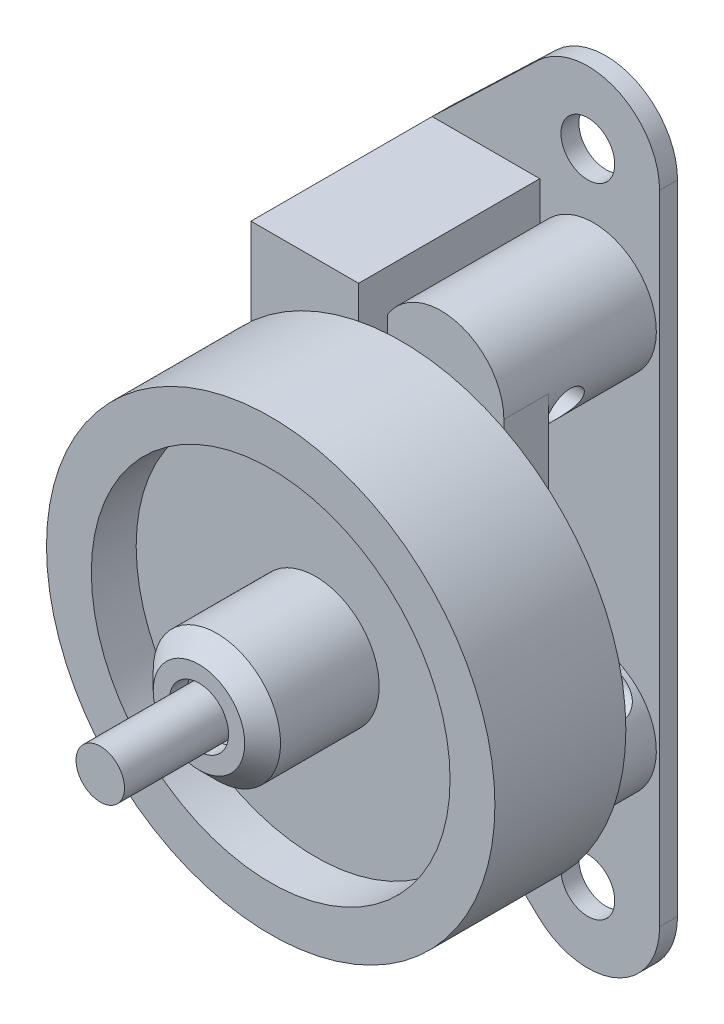
SolidWorks part; units mm, degrees
ref_plane "Front Plane" through (0, 0, 0) normal (0, 0, 1) x (1, 0, 0)
ref_plane "Top Plane" through (0, 0, 0) normal (0, 1, 0) x (1, 0, 0)
ref_plane "Right Plane" through (0, 0, 0) normal (1, 0, 0) x (0, 0, -1)
sketch "Sketch1" plane through (0, 0, 0) normal (0, 0, 1) x (1, 0, 0)
  line L0 (47.18, 17.78) -> (47.18, -17.78)
  line L1 (39.18, 17.78) -> (39.18, -17.78)
  circle A0 centre (43.18, 17.78) radius 1.5 construction
  circle A1 centre (43.18, 17.78) radius 1.5
  circle A2 centre (43.18, -17.78) radius 1.5 construction
  circle A3 centre (43.18, -17.78) radius 1.5
  circle A4 centre (43.18, 17.78) radius 4
  circle A5 centre (43.18, -17.78) radius 4
  dimension "D1" = 8
extrude "Boss-Extrude1" add sketch "Sketch1" along normal blind 1 contours A5 L0 A4 L1 | A4 A1 | A5 A3 region at (43.18, 13.8931, 0) region at (43.18, 0, 0) region at (43.18, -21.6669, 0)
sketch "Sketch2" plane through (0, 0, 1) normal (0, 0, 1) x (1, 0, 0)
  line L0 (40.4119, 20.6675) -> (34.5, 15)
  line L1 (34.5, 15) -> (34.5, -15)
  line L2 (34.5, -15) -> (40.4119, -20.6675)
  line L3 (39.18, 17.78) -> (39.18, -17.78) construction
  line L4 (39.18, 17.78) -> (39.18, -17.78)
  line L5 (48.5, -24.75) -> (48.5, 24.75) construction
  line L7 (34.5, 0) -> (39.18, 0) construction
  arc A0 (47.18, 17.78) -> (39.18, 17.78) centre (43.18, 17.78) ccw construction
  arc A1 (39.18, -17.78) -> (47.18, -17.78) centre (43.18, -17.78) ccw construction
  arc A2 (47.18, 17.78) -> (39.18, 17.78) centre (43.18, 17.78) ccw
  arc A3 (39.18, -17.78) -> (47.18, -17.78) centre (43.18, -17.78) ccw
  line M1 (39.18, 17.78) -> (39.18, -17.78)
  arc M2 (39.18, -17.78) -> (47.18, -17.78) centre (43.18, -17.78) ccw
  arc M4 (47.18, 17.78) -> (39.18, 17.78) centre (43.18, 17.78) ccw
  dimension "D1" = 14
  dimension "D2" = 30
extrude "Boss-Extrude2" add sketch "Sketch2" against normal blind 1 contours L1 L7 L0 M1 M4 | L7 L1 L2 L4 M2 region at (36.953, 8.7197, 1) region at (36.953, -8.7197, 1)
sketch "Sketch3" plane through (0, 0, 1) normal (0, 0, 1) x (1, 0, 0)
  line L0 (34.5, 15) -> (34.5, 11.5) construction
  line L1 (34.5, 15) -> (40.5, 15)
  line L2 (34.5, 15) -> (34.5, 6.75)
  line L3 (34.5, 6.75) -> (40.5, 6.75)
  line L4 (40.5, 15) -> (40.5, 6.75)
  line L5 (34.5, -15) -> (40.5, -15)
  line L6 (34.5, -15) -> (34.5, -3.75)
  line L7 (34.5, -3.75) -> (40.5, -3.75)
  line L8 (40.5, -15) -> (40.5, -3.75)
  line L9 (34.5, 11.5) -> (59.3702, 11.5) construction
  line L10 (34.5, -15) -> (34.5, -11.5) construction
  line L11 (34.5, -11.5) -> (58.5732, -11.5) construction
  line L12 (43.18, 17.78) -> (43.18, 11.5) construction
  line L13 (43.18, -17.78) -> (43.18, -11.5) construction
  dimension "D1" = 10.5
  dimension "D2" = 23
  dimension "D3" = 7.75
  dimension "D4" = 4.75
  dimension "D5" = 6
extrude "Boss-Extrude3" add sketch "Sketch3" along normal blind 7.1
sketch "Sketch4" plane through (0, 0, 1) normal (0, 0, 1) x (1, 0, 0)
  line L0 (37.5, 6.75) -> (37.5, -3.75) construction
  line L1 (34.5, 6.75) -> (40.5, 6.75) construction
  line L2 (40.5, -3.75) -> (34.5, -3.75) construction
  line L3 (37.5, 1.5) -> (43.5, 1.5) construction
  line L4 (34.5, 6.75) -> (34.5, -3.75) construction
  line L5 (40.5, 10.875) -> (56.47, 10.875) construction
  line L6 (40.5, 6.75) -> (40.5, 15) construction
  line L7 (40.5, -9.375) -> (56.47, -9.375) construction
  line L8 (40.5, -15) -> (40.5, -3.75) construction
  line L9 (43.5, 1.5) -> (43.5, -9.375) construction
  line L10 (43.5, 1.5) -> (43.5, 10.875) construction
  circle A0 centre (43.5, 1.5) radius 2.1
  circle A1 centre (43.5, 10.875) radius 3.5
  circle A2 centre (43.5, -9.375) radius 3.5
  line M3 (40.5, -3.75) -> (40.5, -15)
  line M11 (40.5, 15) -> (40.5, 6.75)
  dimension "D2" = 4.2
  dimension "D3" = 7
  dimension "D1" = 9
extrude "Boss-Extrude4" add sketch "Sketch4" along normal blind 6 contours A1 M11 | A2 M3 region at (43.6048, 10.875, 1) region at (43.6048, -9.375, 1)
sketch "Sketch5" plane through (0, 0, 7) normal (0, 0, 1) x (1, 0, 0)
  line L0 (47, 10.875) -> (47, -9.375)
  line L1 (40, 10.875) -> (40, -9.375)
  arc A0 (40.5, 9.0722) -> (40.5, 12.6778) centre (43.5, 10.875) ccw construction
  circle A1 centre (43.5, 10.875) radius 3.5
  arc A2 (40.5, -11.1778) -> (40.5, -7.5722) centre (43.5, -9.375) ccw construction
  circle A3 centre (43.5, -9.375) radius 3.5
  line M3 (40.5, 12.6778) -> (40.5, 9.0722)
  arc M4 (40.5, 9.0722) -> (40.5, 12.6778) centre (43.5, 10.875) ccw
extrude "Boss-Extrude5" add sketch "Sketch5" along normal blind 1.5 contours M4 M3 | A3 L0 A1 L1 M4 | A3 region at (43.6048, 10.875, 7) region at (43.5, 0.75, 7) region at (43.5, -9.375, 7)
extrude "Cut-Extrude1" cut sketch "Sketch4<3>" along normal blind 12 contours A0 region at (43.5, 1.5, 1)
sketch "Sketch4<3>" plane through (0, 0, 1) normal (0, 0, 1) x (1, 0, 0) same geometry as "Sketch4"
sketch "Sketch6" plane through (34.5, 0, 0) normal (-1, 0, 0) x (0, 0, 1)
  line L0 (8.1, 15) -> (8.1, 6.75) construction
  line L1 (8.1, 11.5) -> (0, 11.5) construction
  line L2 (8.1, 11.5) -> (8.1, -11.5) construction
  line L3 (8.1, -11.5) -> (0, -11.5) construction
  line L4 (0, 11.5) -> (0, -11.5) construction
  line L5 (0, 15) -> (0, -15) construction
  line L6 (8.1, -3.75) -> (8.1, -15) construction
  line L8 (0, 0) -> (8.1, 0) construction
  circle A0 centre (5.8, 9.5) radius 1
  circle A1 centre (2.3, -6.5) radius 1
  point P8 (0, 0)
  dimension "D2" = 16
  dimension "D3" = 2
  dimension "D1" = 23
  dimension "D4" = 2.3
  dimension "D5" = 2.3
  dimension "D6" = 2
  dimension "D7" = 5
extrude "Cut-Extrude2" cut sketch "Sketch6" against normal blind 13
sketch "Sketch7" plane through (0, 0, 8.5) normal (0, 0, 1) x (1, 0, 0)
  circle A0 centre (43.5, 1.5) radius 3.7
  dimension "D1" = 7.4
extrude "Boss-Extrude6" add sketch "Sketch7" along normal blind 3.2 separate body
sketch "Sketch8" plane through (0, 0, 11.7) normal (0, 0, 1) x (1, 0, 0)
  circle A0 centre (43.5, 1.5) radius 12.5
  dimension "D1" = 25
extrude "Boss-Extrude7" add sketch "Sketch8" along normal blind 7.3
sketch "Sketch9" plane through (0, 0, 19) normal (0, 0, 1) x (1, 0, 0)
  circle A0 centre (43.5, 1.5) radius 2
  dimension "D1" = 4
extrude "Boss-Extrude8" add sketch "Sketch9" along normal blind 1.8
sketch "Sketch10" plane through (0, 0, 20.8) normal (0, 0, 1) x (1, 0, 0)
  circle A0 centre (43.5, 1.5) radius 1.35
  dimension "D1" = 2.7
extrude "Boss-Extrude9" add sketch "Sketch10" along normal blind 7.7
sketch "Sketch11" plane through (0, 0, 8.1) normal (0, 0, 1) x (1, 0, 0)
  line L1 (40, 6.75) -> (40.5, 6.75)
  line L2 (40, 6.75) -> (40, 15)
  line L3 (40, 15) -> (40.5, 15)
  line L4 (34.5, 15) -> (34.5, 6.75)
  line L5 (34.5, 6.75) -> (40, 6.75)
  line L6 (40.5, 12.6778) -> (40.5, 15)
  line L7 (40.5, 15) -> (34.5, 15)
  line L8 (34.5, 15) -> (34.5, 6.75)
  line L9 (34.5, 6.75) -> (40, 6.75)
  line L10 (40.5, 12.6778) -> (40.5, 15)
  line L11 (40.5, 15) -> (34.5, 15)
  line L12 (34.5, -3.75) -> (34.5, -15)
  line L13 (34.5, -15) -> (40.5, -15)
  line L14 (40.5, -15) -> (40.5, -11.1778)
  line L15 (40, -3.75) -> (34.5, -3.75)
  line L16 (34.5, -3.75) -> (34.5, -15)
  line L17 (34.5, -15) -> (40.5, -15)
  line L18 (40.5, -15) -> (40.5, -11.1778)
  line L19 (40, -3.75) -> (34.5, -3.75)
  line L20 (40.5, 6.75) -> (40.5, 15)
  line L21 (40, -9.375) -> (40, -3.75)
  line L22 (40.5, 9.0722) -> (40.5, 12.6778)
  line L23 (40.5, 9.0722) -> (40.5, 12.6778)
  line L24 (40, 6.75) -> (40, 10.875)
  line L25 (40, 6.75) -> (40, 10.875)
  line L26 (40, -9.375) -> (40, -3.75)
  line L27 (40.5, -15) -> (40, -15)
  line L28 (40.5, -15) -> (40.5, -3.75)
  line L29 (40.5, -3.75) -> (40, -3.75)
  line L30 (40, -15) -> (40, -3.75)
  arc A1 (40, 10.875) -> (40.5, 9.0722) centre (43.5, 10.875) ccw
  arc A2 (40, 10.875) -> (40.5, 9.0722) centre (43.5, 10.875) ccw
  arc A3 (40, -9.375) -> (40.5, -11.1778) centre (43.5, -9.375) ccw
  arc A4 (40, -9.375) -> (40.5, -11.1778) centre (43.5, -9.375) ccw
  line M9 (34.5, 15) -> (34.5, 6.75)
  line M10 (34.5, 6.75) -> (40, 6.75)
  line M11 (40.5, 12.6778) -> (40.5, 15)
  line M12 (40.5, 15) -> (34.5, 15)
  arc M13 (40, 10.875) -> (40.5, 9.0722) centre (43.5, 10.875) ccw
  line M14 (40.5, 9.0722) -> (40.5, 12.6778)
  line M15 (40, 6.75) -> (40, 10.875)
  dimension "D1" = 0
  dimension "D2" = 0
extrude "Boss-Extrude10" add sketch "Sketch11" along normal blind 2 contours L17 L30 L26 L19 L16 | A4 L30 L17 L18 | L26 A4 L28 L29 | L2 M15 M12 M9 M10 | L1 L20 M13 M15 | L2 M13 M14 M11 M12 region at (40.2295, 8.2331, 8.1) region at (37.25, 10.875, 8.1) region at (40.2611, 12.3108, 8.1) region at (37.25, -9.375, 8.1) region at (40.2587, -7.1856, 8.1) region at (40.2365, -12.7774, 8.1)
sketch "Sketch13" plane through (0, 0, 1) normal (0, 0, 1) x (1, 0, 0)
  line L0 (34.5, 6.75) -> (40.5, 6.75) construction
  line L1 (34.5, 6.75) -> (40.5, 6.75)
  line L2 (40.5, -3.75) -> (34.5, -3.75) construction
  line L3 (40.5, -3.75) -> (34.5, -3.75)
  line L4 (40.5, 12.6778) -> (40.5, 6.75) construction
  line L5 (40.5, 6.75) -> (44.1464, 7.4352)
  line L6 (40.5, -3.75) -> (45.1769, -6.3029)
  line L7 (40.5, -3.75) -> (40.5, -11.1778) construction
  line L8 (40.5, -3.75) -> (40.5, -11.1778)
  line L9 (40.5, 12.6778) -> (40.5, 6.75)
  arc A0 (47, 10.875) -> (40.5, 12.6778) centre (43.5, 10.875) ccw construction
  arc A1 (40.5, 9.0722) -> (40.5, 12.6778) centre (43.5, 10.875) ccw
  arc A2 (40.5, -11.1778) -> (40.5, -7.5722) centre (43.5, -9.375) ccw construction
  arc A3 (40.5, -11.1778) -> (40.5, -7.5722) centre (43.5, -9.375) ccw
  line M4 (40.5, -3.75) -> (40.5, -7.5722)
  arc M5 (40.5, -7.5722) -> (40.5, -11.1778) centre (43.5, -9.375) cw
  arc M15 (40.5, 12.6778) -> (40.5, 9.0722) centre (43.5, 10.875) cw
  line M16 (40.5, 9.0722) -> (40.5, 6.75)
extrude "Boss-Extrude11" add sketch "Sketch13" along normal up to surface (6 mm away) contours L6 M4 M5 | L5 M16 M15 region at (41.3764, 7.5705, 1) region at (41.6732, -5.4861, 1) up to face at (45.6, 1.5, 7)
sketch "Sketch14" plane through (34.5, 0, 0) normal (-1, 0, 0) x (0, 0, 1)
  circle A0 centre (5.8, 9.5) radius 1 construction
  circle A1 centre (5.8, 9.5) radius 1
  circle A2 centre (2.3, -6.5) radius 1 construction
  circle A3 centre (2.3, -6.5) radius 1
extrude "Cut-Extrude3" cut sketch "Sketch14" against normal through all
sketch "Sketch15" plane through (0, 0, 8.5) normal (0, 0, 1) x (1, 0, 0)
  line L0 (40, 6.75) -> (40, -3.75) construction
  line L1 (40, 6.75) -> (40, -3.75)
  circle A0 centre (43.5, 1.5) radius 5
  dimension "D1" = 10
extrude "Boss-Extrude12" add sketch "Sketch15" against normal up to surface (1.5 mm away) contours L1 A0 region at (39.3915, 1.5, 8.5) up to face at (45.6, 1.5, 7)
sketch "Sketch16" plane through (0, 0, 7) normal (0, 0, -1) x (-1, 0, 0)
  circle A0 centre (-43.5, 1.5) radius 2.1 construction
  circle A1 centre (-43.5, 1.5) radius 2.1
extrude "Boss-Extrude13" add sketch "Sketch16" against normal blind 0.2
sketch "Sketch17" plane through (0, 0, 8.5) normal (0, 0, 1) x (1, 0, 0)
  line L7 (40.5, 12.6778) -> (40.5, 6.75)
  line L8 (40.5, 6.75) -> (40, 6.75)
  line L9 (40, 6.75) -> (40, 5.0707)
  line L10 (40, -2.0707) -> (40, -3.75)
  line L11 (40, -3.75) -> (40.5, -3.75)
  line L12 (40.5, -3.75) -> (40.5, -11.1778)
  line L13 (47, -9.375) -> (47, 10.875)
  line L14 (40.5, 12.6778) -> (40.5, 6.75)
  line L15 (40.5, 6.75) -> (40, 6.75)
  line L16 (40, 6.75) -> (40, 5.0707)
  line L17 (40, -2.0707) -> (40, -3.75)
  line L18 (40, -3.75) -> (40.5, -3.75)
  line L19 (40.5, -3.75) -> (40.5, -11.1778)
  line L20 (47, -9.375) -> (47, 10.875)
  circle A0 centre (43.5, 1.5) radius 2.1 construction
  circle A1 centre (43.5, 1.5) radius 2.1
  arc A3 (40, 5.0707) -> (40, -2.0707) centre (43.5, 1.5) ccw
  arc A4 (40.5, -11.1778) -> (47, -9.375) centre (43.5, -9.375) ccw
  arc A5 (47, 10.875) -> (40.5, 12.6778) centre (43.5, 10.875) ccw
  arc A6 (40, 5.0707) -> (40, -2.0707) centre (43.5, 1.5) ccw
  arc A7 (40.5, -11.1778) -> (47, -9.375) centre (43.5, -9.375) ccw
  arc A8 (47, 10.875) -> (40.5, 12.6778) centre (43.5, 10.875) ccw
  dimension "D1" = 0
extrude "Boss-Extrude14" add sketch "Sketch17" along normal blind 1
sketch "Sketch18" plane through (0, 0, 10.1) normal (0, 0, 1) x (1, 0, 0)
  line L4 (40.5, -15) -> (40.5, -3.75)
  line L5 (40.5, -3.75) -> (34.5, -3.75)
  line L6 (34.5, -3.75) -> (34.5, -15)
  line L7 (34.5, -15) -> (40.5, -15)
  line L8 (40.5, -15) -> (40.5, -3.75)
  line L9 (40.5, -3.75) -> (34.5, -3.75)
  line L10 (34.5, -3.75) -> (34.5, -15)
  line L11 (34.5, -15) -> (40.5, -15)
  line L12 (40.5, 6.75) -> (40.5, 15)
  line L13 (40.5, 15) -> (34.5, 15)
  line L14 (34.5, 15) -> (34.5, 6.75)
  line L15 (34.5, 6.75) -> (40.5, 6.75)
  line L16 (40.5, 6.75) -> (40.5, 15)
  line L17 (40.5, 15) -> (34.5, 15)
  line L18 (34.5, 15) -> (34.5, 6.75)
  line L19 (34.5, 6.75) -> (40.5, 6.75)
  dimension "D1" = 0
  dimension "D2" = 0
extrude "Boss-Extrude15" add sketch "Sketch18" along normal blind 1
sketch "Sketch19" plane through (0, 0, 19) normal (0, 0, 1) x (1, 0, 0)
  circle A0 centre (43.5, 1.5) radius 2 construction
  circle A1 centre (43.5, 1.5) radius 2
  circle A2 centre (43.5, 1.5) radius 10
  dimension "D1" = 20
extrude "Cut-Extrude4" cut sketch "Sketch19" against normal blind 2.5
sketch "Sketch20" plane through (0, 0, 16.5) normal (0, 0, 1) x (1, 0, 0)
  circle A0 centre (43.5, 1.5) radius 2.25
  circle A1 centre (43.5, 1.5) radius 3.55
  dimension "D1" = 4.5
  dimension "D2" = 1.3
extrude "Boss-Extrude16" add sketch "Sketch20" along normal blind 6.5 separate body
sketch "Sketch21" plane through (0, 0, 23) normal (0, 0, 1) x (1, 0, 0)
  circle A0 centre (43.5, 1.5) radius 1.65
  circle A1 centre (43.5, 1.5) radius 2.25 construction
  circle A2 centre (43.5, 1.5) radius 2.25
  dimension "D1" = 3.3
extrude "Boss-Extrude17" add sketch "Sketch21" against normal blind 1
chamfer "Chamfer1" distance 1 angle 45 1 edges at (47.05, 1.5, 23)
